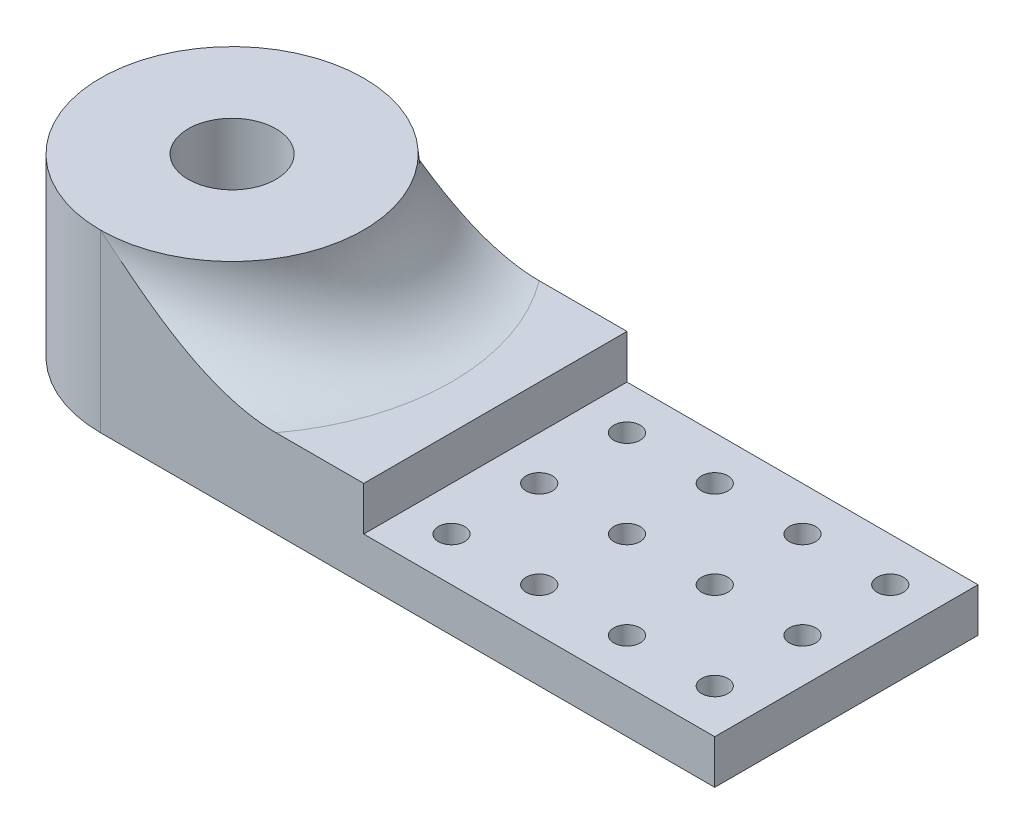
SolidWorks part; units mm, degrees
ref_plane "Front Plane" through (0, 0, 0) normal (0, 0, 1) x (1, 0, 0)
ref_plane "Top Plane" through (0, 0, 0) normal (0, 1, 0) x (1, 0, 0)
ref_plane "Right Plane" through (0, 0, 0) normal (1, 0, 0) x (0, 0, -1)
sketch "Sketch1" plane through (0, 0, 0) normal (0, 1, 0) x (1, 0, 0)
  line L1 (0, 15) -> (70, 15)
  line L2 (0, 15) -> (0, -15) construction
  line L3 (0, -15) -> (70, -15)
  line L4 (70, 15) -> (70, -15)
  line L6 (-80, 0) -> (0, 0) construction
  circle A0 centre (0, 0) radius 5
  arc A1 (0, 15) -> (0, -15) centre (0, 0) ccw
  dimension "D1" = 10
  dimension "D2" = 30
  dimension "D4" = 70
  dimension "D5" = 80
extrude "Boss-Extrude1" add sketch "Sketch1" along normal mid plane 10
sketch "Sketch2" plane through (0, 5, 0) normal (0, 1, 0) x (1, 0, 0)
  circle A0 centre (0, 0) radius 5
  circle A1 centre (0, 0) radius 15
extrude "Boss-Extrude2" add sketch "Sketch2" along normal blind 10
fillet "Fillet1" radius 10 1 edges at (15, 5, 0)
sketch "Sketch3" plane through (0, 5, 0) normal (0, 1, 0) x (1, 0, 0)
  line L1 (20, -15) -> (70, -15) construction
  line L2 (70, -15) -> (70, 15)
  line L3 (70, 15) -> (30, 15)
  line L4 (70, 15) -> (20, 15) construction
  line L5 (30, 15) -> (30, -15)
  line L6 (30, -15) -> (70, -15)
  dimension "D1" = 40
extrude "Cut-Extrude1" cut sketch "Sketch3" against normal blind 5
sketch "Sketch4" plane through (0, 0, 0) normal (0, 1, 0) x (1, 0, 0)
  line L1 (70, 0) -> (30, 0) construction
  line L2 (70, -15) -> (70, 15) construction
  line L3 (30, 15) -> (30, -15) construction
  circle A1 centre (65, 0) radius 1.5
  circle A2 centre (55, 0) radius 1.5
  circle A3 centre (45, 0) radius 1.5
  circle A4 centre (35, 0) radius 1.5
  dimension "D1" = 3
  dimension "D2" = 3
  dimension "D3" = 3
  dimension "D4" = 3
  dimension "D5" = 10
  dimension "D6" = 5
  dimension "D7" = 10
  dimension "D8" = 10
extrude "Cut-Extrude2" cut sketch "Sketch4" against normal blind 5 contours A4 | A3 | A2 | A1
pattern_linear "LPattern1" count 2 spacing 10 along (0, 0, -1) count 2 spacing 10 along (0, 0, 1) of "Cut-Extrude2"
